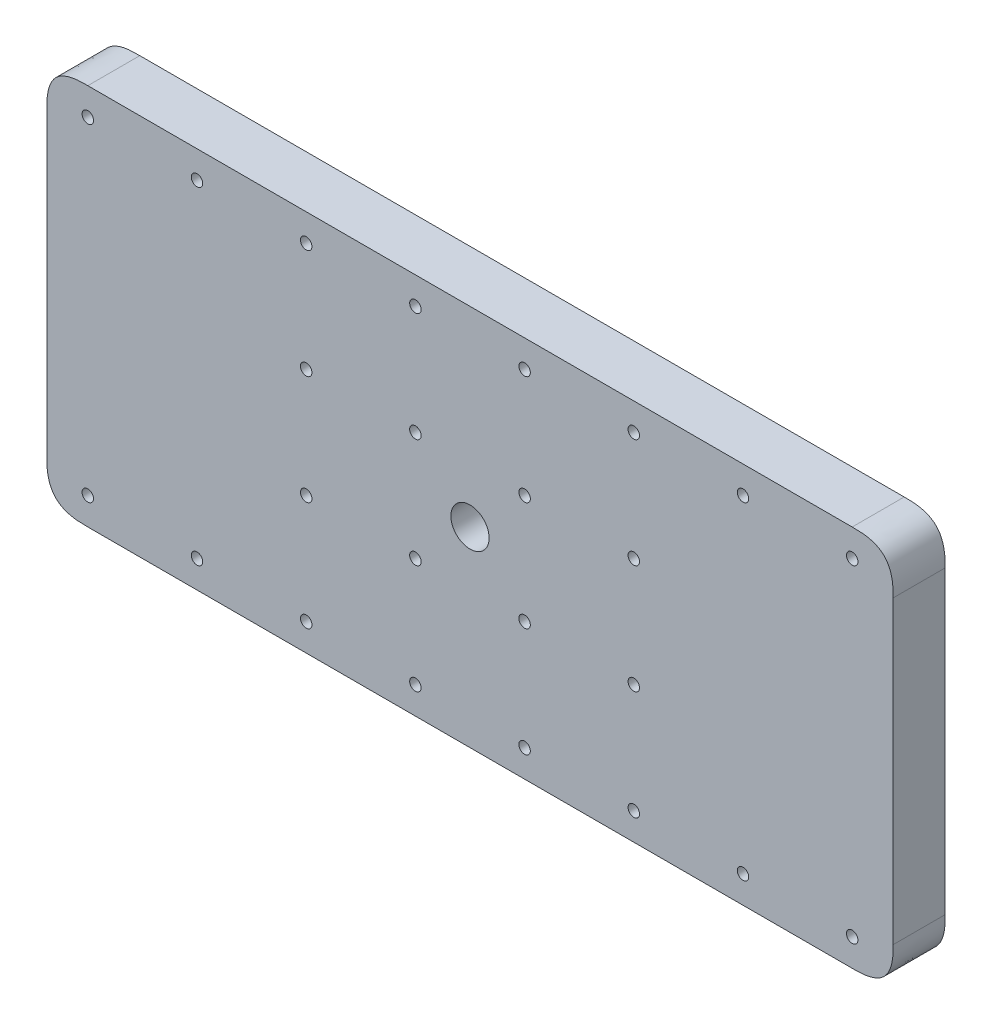
SolidWorks part; units mm, degrees
ref_plane "Front Plane" through (0, 0, 0) normal (0, 0, 1) x (1, 0, 0)
ref_plane "Top Plane" through (0, 0, 0) normal (0, 1, 0) x (1, 0, 0)
ref_plane "Right Plane" through (0, 0, 0) normal (1, 0, 0) x (0, 0, -1)
sketch "Sketch1" plane through (0, 0, 0) normal (0, 0, 1) x (1, 0, 0)
  line L1 (-155, 70) -> (155, 70)
  line L2 (-155, 70) -> (-155, -70)
  line L3 (-155, -70) -> (155, -70)
  line L4 (155, 70) -> (155, -70)
  line L5 (-155, 70) -> (155, -70) construction
  line L6 (-155, -70) -> (155, 70) construction
  point P0 (0, 0)
  dimension "D1" = 310
  dimension "D2" = 140
extrude "Boss-Extrude1" add sketch "Sketch1" along normal blind 19.05
sketch "Sketch5" plane through (0, 0, 19.05) normal (0, 0, 1) x (1, 0, 0)
  line L1 (-140, 60) -> (140, 60) construction
  line L2 (-140, 60) -> (-140, -60) construction
  line L3 (-140, -60) -> (140, -60) construction
  line L4 (140, 60) -> (140, -60) construction
  line L8 (-140, 60) -> (140, -60) construction
  point P0 (-140, 60)
  point P14 (-140, 60)
  dimension "D1" = 280
  dimension "D2" = 120
hole_wizard "Tap Drill for M5x0.8 Tap1" positions "Sketch5" profile "Sketch6" hole size "M5x0.8" standard "ANSI Metric" end condition up to next
sketch "Sketch6" plane through (-140, 60, 19.05) normal (1, 0, 0) x (0, -1, 0)
  line L0 (0, 0) -> (0, 19.05)
  line L1 (0, 19.05) -> (2.1, 19.05)
  line L2 (2.1, 19.05) -> (2.1, 0)
  line L5 (2.1, 0) -> (0, 0)
  line L11 (0, -6.35) -> (0, 107.95) construction
  dimension "Thru Hole Dia." = 4.2
  dimension "Thru Hole Depth" = 19.05
pattern_linear "LPattern1" count 8 spacing 40 along (1, 0, 0) count 4 spacing 40 along (0, -1, 0) skipping (0, 1), (0, 2), (1, 1), (1, 2), (6, 1), (6, 2), (7, 1), (7, 2) of "Tap Drill for M5x0.8 Tap1"
fillet "Fillet1" radius 15 4 edges at (155, -70, 9.525) (155, 70, 9.525) (-155, 70, 9.525) (-155, -70, 9.525) curvature continuous yes
sketch "Sketch10" plane through (0, 0, 0) normal (0, 0, -1) x (-1, 0, 0)
  point P0 (137.5, -12.5)
  point P3 (137.5, 12.5)
  point P6 (112.5, 12.5)
  point P9 (112.5, -12.5)
  point P12 (-112.5, -12.5)
  point P15 (-137.5, -12.5)
  point P18 (-112.5, 12.5)
  point P21 (-137.5, 12.5)
hole_wizard "M5 Clearance Hole1" positions "Sketch10" profile "Sketch9" hole size "M5" standard "ANSI Metric"
sketch "Sketch9" plane through (-137.5, -12.5, 0) normal (1, 0, 0) x (0, 1, 0)
  line L0 (0, 0) -> (0, 14.2923)
  line L1 (0, 14.2923) -> (2.65, 12.7)
  line L2 (2.65, 12.7) -> (2.65, 0)
  line L5 (2.65, 0) -> (0, 0)
  line L10 (0, 14.2923) -> (-2.65, 12.7) construction
  line L11 (0, -6.35) -> (0, 107.95) construction
  dimension "Hole Dia." = 5.3
  dimension "Hole Depth" = 12.7
  dimension "Drill Angle" = 118
sketch "Sketch11" plane through (0, 0, 19.05) normal (0, 0, 1) x (1, 0, 0)
  line L0 (0, 70) -> (0, -70) construction
  line L1 (140, 70) -> (-140, 70) construction
  line L2 (-140, -70) -> (140, -70) construction
  point P6 (0, 0)
sketch "Sketch14" plane through (0, 0, 19.05) normal (0, 0, 1) x (1, 0, 0)
  point P0 (0, 0)
hole_wizard "Tap Drill for M16x2.0 Tap1" positions "Sketch14" profile "Sketch13" hole size "M16x2.0" standard "ANSI Metric" end condition through all
sketch "Sketch13" plane through (0, 0, 19.05) normal (1, 0, 0) x (0, -1, 0)
  line L0 (0, 0) -> (0, 19.1)
  line L1 (0, 19.1) -> (7, 19.1)
  line L2 (7, 19.1) -> (7, 0)
  line L5 (7, 0) -> (0, 0)
  line L11 (0, -6.35) -> (0, 107.95) construction
  dimension "Thru Hole Dia." = 14
  dimension "Thru Hole Depth" = 19.1
